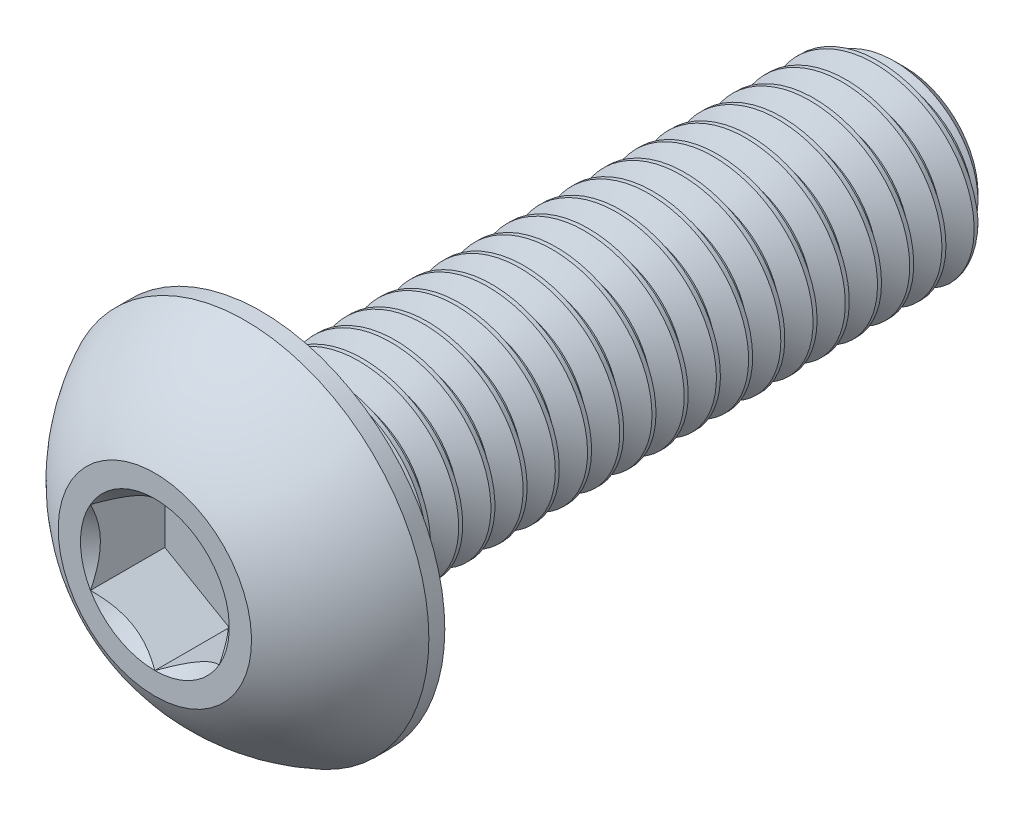
SolidWorks part; units mm, degrees
ref_plane "Front" through (0, 0, 0) normal (0, 0, 1) x (1, 0, 0)
ref_plane "Top" through (0, 0, 0) normal (0, 1, 0) x (1, 0, 0)
ref_plane "Right" through (0, 0, 0) normal (1, 0, 0) x (0, 0, -1)
sketch "Sketch1" plane through (0, 0, 0) normal (1, 0, 0) x (0, 0, -1)
  line L2 (1.65, 1.5) -> (11.65, 1.5)
  line L3 (11.65, 1.5) -> (11.65, 0)
  line L4 (11.65, 0) -> (1.65, 0)
  line L6 (1.4025, 2.85) -> (1.65, 2.85) construction
  line L7 (11.65, 1.5) -> (11.65, -1.5) construction
  line L8 (0, 0) -> (1.65, 0) construction
  line L9 (1.65, 2.85) -> (1.65, -2.85) construction
  line L11 (1.65, 1.5) -> (1.65, 0)
  line L13 (0, 1) -> (0, -1) construction
  line L14 (0, 1) -> (0, 1.5) construction
  arc A3 (0, 1.5) -> (1.4025, 2.85) centre (2.7948, 0) cw construction
  dimension "D1" = 0.2475
  dimension "Head Ht" = 1.65
  dimension "Head Dia" = 5.7
  dimension "Dia" = 3
  dimension "Lg" = 10
  dimension "Hex" = 2
revolve "Revolve1" add sketch "Sketch1" angle 360 mid plane about L4
sketch "Sketch3" plane through (0, 0, -11.65) normal (0, 0, -1) x (-1, 0, 0)
  circle A0 centre (0, 0) radius 1.5
curve "Helix/Spiral1" pitch 0.5 height 10.5 radius 1.5 centre (0, 0, -11.65) axis (0, 0, 1) start towards (0, 1, 0)
sketch "Sketch2" plane through (0, 0, 0) normal (1, 0, 0) x (0, 0, -1)
  line L0 (11.65, 1.5) -> (12.0875, 1.5)
  line L1 (12.0875, 1.5) -> (11.9, 1.1752)
  line L2 (11.9, 1.1752) -> (11.8375, 1.1752)
  line L3 (11.8375, 1.1752) -> (11.65, 1.5)
  line L4 (11.7437, 1.3376) -> (11.9937, 1.3376) construction
  dimension "D1" = 60
  dimension "D2" = 0.0625
  dimension "D3" = 0.25
chamfer "Chamfer1" distance 0.375 angle 45 1 edges at (0, 1.5, -11.65)
sweep "Cut-Sweep1" cut profiles "Sketch2" path "Helix/Spiral1"
sketch "Sketch7" plane through (0, 0, 0) normal (1, 0, 0) x (0, 0, -1)
  line L6 (1.4025, 2.85) -> (1.65, 2.85) construction
  line L8 (0, 0) -> (1.65, 0) construction
  line L11 (1.65, 2.85) -> (1.65, -2.85) construction
  line L12 (1.4025, 2.85) -> (1.65, 2.85)
  line L13 (0, 0) -> (1.65, 0)
  line L14 (0, 1) -> (0, -1) construction
  line L15 (1.65, 2.85) -> (1.65, 0)
  line L16 (0, 1.5) -> (0, 0)
  arc A2 (1.4025, 2.85) -> (0, 1.5) centre (2.7948, 0) ccw construction
  arc A3 (1.4025, 2.85) -> (0, 1.5) centre (2.7948, 0) ccw
revolve "Revolve2" add sketch "Sketch7" angle 360 mid plane about L13
sketch "Sketch5" plane through (0, 0, 0) normal (0, 0, 1) x (1, 0, 0)
  line L1 (1, -0.5774) -> (1, 0.5774)
  line L2 (1, 0.5774) -> (0, 1.1547)
  line L3 (0, 1.1547) -> (-1, 0.5774)
  line L4 (-1, 0.5774) -> (-1, -0.5774)
  line L5 (-1, -0.5774) -> (0, -1.1547)
  line L6 (0, -1.1547) -> (1, -0.5774)
  circle A0 centre (0, 0) radius 1 construction
extrude "Cut-Extrude2" cut sketch "Sketch5" against normal blind 1.155
sketch "Sketch6" plane through (0, 0, 0) normal (0, 0, 1) x (1, 0, 0)
  circle A0 centre (0, 0) radius 1.1547
extrude "Cut-Extrude3" cut sketch "Sketch6" against normal blind 1.155 draft 45
sketch "Sketch9" [suppressed] plane through (0, 0, -6.6) normal (0, 0, 1) x (1, 0, 0)
  circle A2 centre (0, 0) radius 6
extrude "Boss-Extrude2" [suppressed] add sketch "Sketch9" against normal offset from surface (19 mm away) 32 up to face at (0, 1.125, -11.65)
sketch "Sketch10" plane through (0, 0, 0) normal (1, 0, 0) x (0, 0, -1)
  line L0 (11.65, 1.5) -> (11.65, -1.5) construction
  point P0 (10.9, -1.5)
  dimension "D1" = 0.75
equation "\"D3@Helix/Spiral1\" = \"Lg@Sketch1\" + \"D4@Helix/Spiral1\""
equation "\"D2@Sketch2\" = \"D4@Helix/Spiral1\" * .125"
equation "\"D3@Sketch2\" = \"D4@Helix/Spiral1\" * .5"
equation "\"D1@Chamfer1\" = \"D4@Helix/Spiral1\" * .75"
equation "\"D1@Cut-Extrude2\" = \"Head Ht@Sketch1\" * .7"
equation "\"D1@Sketch1\" = \"Head Ht@Sketch1\" * .15"
equation "\"D1@Sketch10\" = \"D4@Helix/Spiral1\" * 1.5"
equation "\"D1@Cut-Extrude3\" = \"D1@Cut-Extrude2\""
